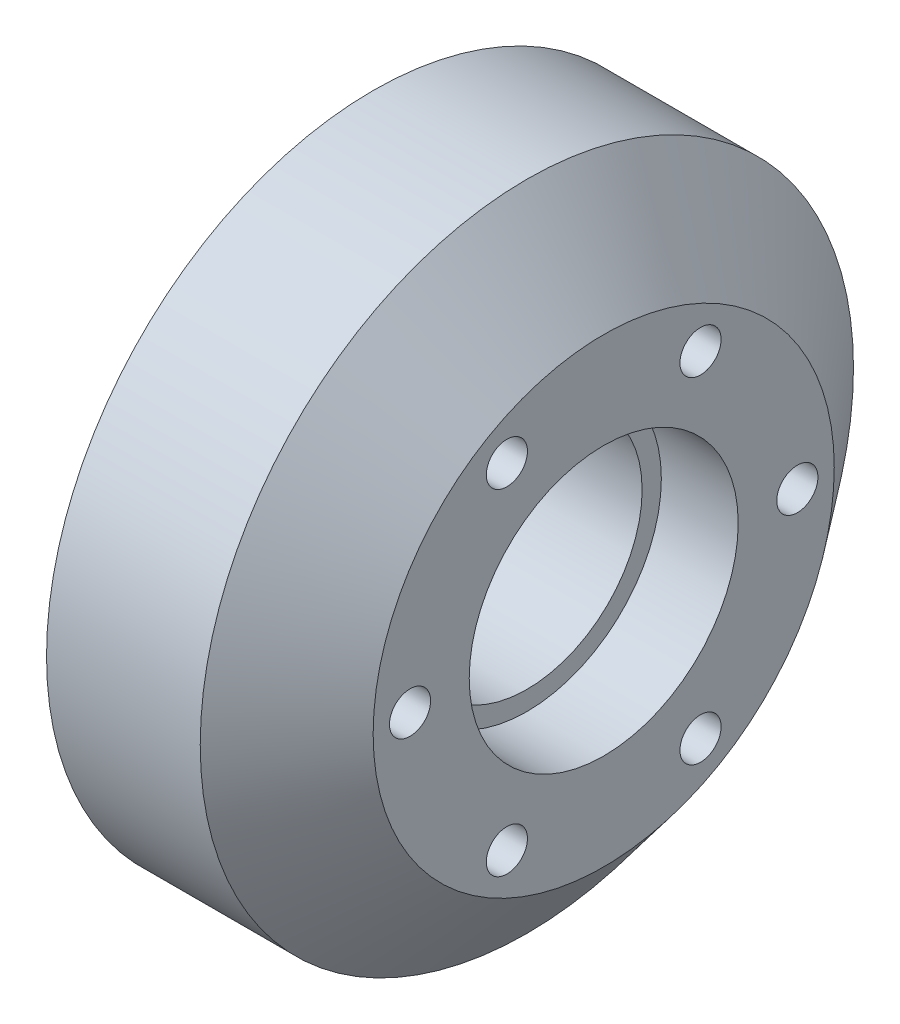
SolidWorks part; units mm, degrees
ref_plane "Front" through (0, 0, 0) normal (0, 0, 1) x (1, 0, 0)
ref_plane "Top" through (0, 0, 0) normal (0, 1, 0) x (1, 0, 0)
ref_plane "Right" through (0, 0, 0) normal (1, 0, 0) x (0, 0, -1)
sketch "Sketch1" plane through (0, 0, 0) normal (0, 0, 1) x (1, 0, 0)
  line L0 (0, 26.9875) -> (0, 9.525)
  line L1 (0, 9.525) -> (12.7, 9.525)
  line L2 (12.7, 9.525) -> (12.7, 11.1125)
  line L3 (12.7, 11.1125) -> (19.05, 11.1125)
  line L4 (19.05, 11.1125) -> (19.05, 19.05)
  line L5 (19.05, 19.05) -> (12.7, 26.9875)
  line L6 (12.7, 26.9875) -> (0, 26.9875)
  line L7 (0, 0) -> (-10.95, 0) construction
  dimension "D1" = 19.05
  dimension "D2" = 53.975
  dimension "D3" = 38.1
  dimension "D4" = 12.7
  dimension "D5" = 19.05
  dimension "D6" = 6.35
  dimension "D7" = 22.225
revolve "Revolve1" add sketch "Sketch1" angle 360 about L7
sketch "Sketch2" plane through (0, 0, 0) normal (0, 1, 0) x (1, 0, 0)
  line L0 (0, 0) -> (24.0323, 0) construction
  line L1 (19.05, 16) -> (23.214, 16) construction
  line L2 (19.05, -19.05) -> (19.05, 19.05) construction
  line L3 (19.05, 16) -> (0, 16)
  line L4 (0, 26.9875) -> (0, -26.9875) construction
  line L5 (0, 16) -> (0, 19.25)
  line L6 (0, 19.25) -> (12.7, 19.25)
  line L7 (12.7, 19.25) -> (12.7, 17.7)
  line L8 (12.7, 17.7) -> (19.05, 17.7)
  line L9 (19.05, 17.7) -> (19.05, 16)
  dimension "D1" = 3.4
  dimension "D2" = 6.5
  dimension "D3" = 6.35
  dimension "D4" = 32
revolve "Cut-Revolve1" cut sketch "Sketch2" angle 360 about L1
sketch "Sketch3" plane through (0, 0, 0) normal (0, 0, 1) x (1, 0, 0)
  line L0 (0, 20.6375) -> (11.6666, 20.6375)
  line L1 (0, 26.9875) -> (0, -26.9875) construction
  line L2 (11.6666, 20.6375) -> (9.525, 23.8125)
  line L3 (9.525, 23.8125) -> (0, 23.8125)
  line L4 (0, 23.8125) -> (0, 20.6375)
  line L5 (0, 20.6375) -> (-4.5359, 20.6375) construction
  line L6 (0, 0) -> (8.7066, 0) construction
  dimension "D1" = 6.35
  dimension "D2" = 112
  dimension "D3" = 41.275
  dimension "D4" = 9.525
revolve "Cut-Revolve2" cut sketch "Sketch3" angle 360 about L5
pattern_circular "CirPattern1" count 6 over 360 about axis through (0, 0, 0) along (1, 0, 0) of "Cut-Revolve2", "Cut-Revolve1"
